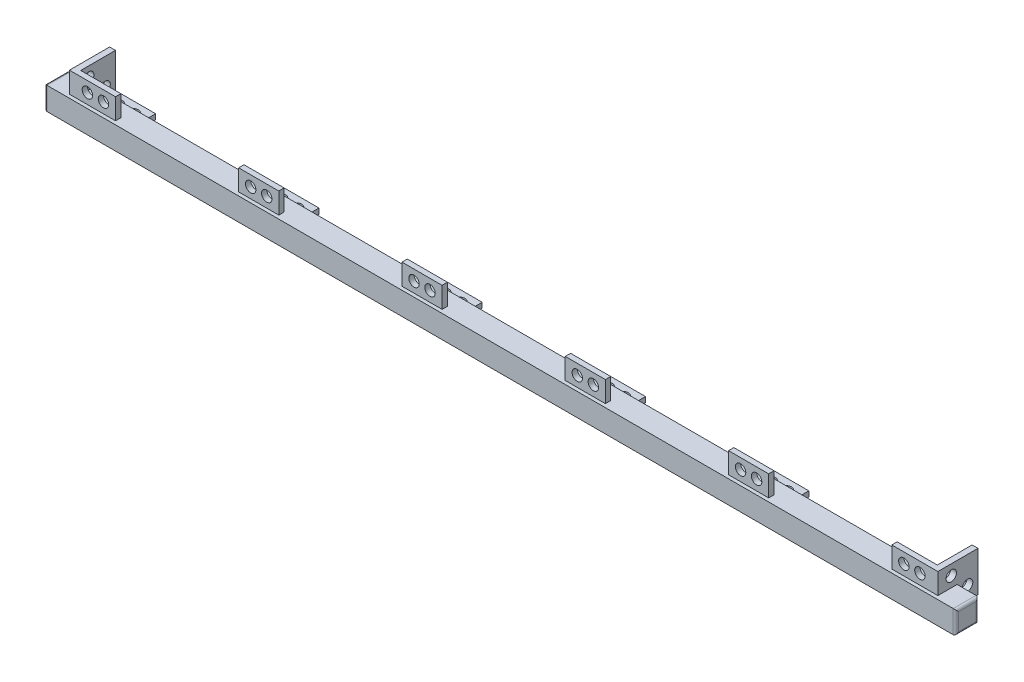
SolidWorks part; units mm, degrees
ref_plane "Front Plane" through (0, 0, 0) normal (0, 0, 1) x (1, 0, 0)
ref_plane "Top Plane" through (0, 0, 0) normal (0, 1, 0) x (1, 0, 0)
ref_plane "Right Plane" through (0, 0, 0) normal (1, 0, 0) x (0, 0, -1)
sketch "Sketch1" plane through (0, 0, 0) normal (1, 0, 0) x (0, 0, -1)
  line L1 (0, 0) -> (8.5, 0)
  line L2 (0, 0) -> (0, 8.5)
  line L3 (0, 8.5) -> (8.5, 8.5)
  line L4 (8.5, 0) -> (8.5, 8.5)
  dimension "D1" = 8.5
  dimension "D2" = 8.5
extrude "Boss-Extrude1" add sketch "Sketch1" along normal blind 340.5
sketch "Sketch2" plane through (0, 8.5, 0) normal (0, 1, 0) x (1, 0, 0)
  line L0 (340.5, 8.5) -> (0, 8.5) construction
  line L1 (6.75, 8.5) -> (333.75, 8.5) construction
  line L2 (6.75, 8.5) -> (6.75, 0) construction
  line L3 (6.75, 0) -> (333.75, 0) construction
  line L4 (333.75, 8.5) -> (333.75, 0) construction
  line L5 (340.5, 0) -> (0, 0) construction
  line L6 (340.5, 8.5) -> (340.5, 0) construction
  line L9 (0, 8.5) -> (0, 0) construction
  line L10 (17.75, 1.3) -> (17.75, 3.3) construction
  line L11 (10.25, 3.3) -> (25.25, 3.3)
  line L12 (10.25, 3.3) -> (10.25, 1.3)
  line L13 (10.25, 1.3) -> (25.25, 1.3)
  line L14 (25.25, 3.3) -> (25.25, 1.3)
  line L15 (71.25, 1.3) -> (86.25, 1.3)
  line L16 (71.25, 3.3) -> (71.25, 1.3)
  line L17 (71.25, 3.3) -> (86.25, 3.3)
  line L18 (86.25, 3.3) -> (86.25, 1.3)
  line L19 (132.25, 1.3) -> (147.25, 1.3)
  line L20 (132.25, 3.3) -> (132.25, 1.3)
  line L21 (132.25, 3.3) -> (147.25, 3.3)
  line L22 (147.25, 3.3) -> (147.25, 1.3)
  line L23 (193.25, 1.3) -> (208.25, 1.3)
  line L24 (193.25, 3.3) -> (193.25, 1.3)
  line L25 (193.25, 3.3) -> (208.25, 3.3)
  line L26 (208.25, 3.3) -> (208.25, 1.3)
  line L27 (254.25, 1.3) -> (269.25, 1.3)
  line L28 (254.25, 3.3) -> (254.25, 1.3)
  line L29 (254.25, 3.3) -> (269.25, 3.3)
  line L30 (269.25, 3.3) -> (269.25, 1.3)
  line L31 (315.25, 1.3) -> (330.25, 1.3)
  line L32 (315.25, 3.3) -> (315.25, 1.3)
  line L33 (315.25, 3.3) -> (330.25, 3.3)
  line L34 (330.25, 3.3) -> (330.25, 1.3)
  point P8 (340.5, 4.25)
  dimension "D1" = 327
  dimension "D2" = 6.75
  dimension "D3" = 6.75
  dimension "D4" = 2
  dimension "D5" = 15
  dimension "D6" = 11
  dimension "D8" = 1.3
  dimension "D7" = 6
extrude "Boss-Extrude2" add sketch "Sketch2" along normal blind 7.8
sketch "Sketch3" plane through (0, 0, -1.3) normal (0, 0, 1) x (1, 0, 0)
  line L0 (10.25, 8.5) -> (25.25, 8.5) construction
  line L3 (10.25, 16.3) -> (10.25, 8.5) construction
  circle A0 centre (14.75, 12.4) radius 1.95
  circle A1 centre (20.75, 12.4) radius 1.95
  circle A2 centre (75.75, 12.4) radius 1.95
  circle A3 centre (81.75, 12.4) radius 1.95
  circle A4 centre (136.75, 12.4) radius 1.95
  circle A5 centre (142.75, 12.4) radius 1.95
  circle A6 centre (197.75, 12.4) radius 1.95
  circle A7 centre (203.75, 12.4) radius 1.95
  circle A8 centre (258.75, 12.4) radius 1.95
  circle A9 centre (264.75, 12.4) radius 1.95
  circle A10 centre (319.75, 12.4) radius 1.95
  circle A11 centre (325.75, 12.4) radius 1.95
  dimension "D6" = 3.9
  dimension "D7" = 3.9
  dimension "D1" = 3.9
  dimension "D2" = 3.9
  dimension "D3" = 6
  dimension "D4" = 4.5
  dimension "D5" = 6
extrude "Cut-Extrude1" cut sketch "Sketch3" against normal blind 7.8
sketch "Sketch4" plane through (0, 0, -8.5) normal (0, 0, -1) x (-1, 0, 0)
  line L0 (-269.25, 1.3) -> (-254.25, 1.3)
  line L1 (-330.25, 3.3) -> (-315.25, 3.3)
  line L2 (-330.25, 3.3) -> (-330.25, 1.3)
  line L3 (-330.25, 1.3) -> (-315.25, 1.3)
  line L4 (-315.25, 3.3) -> (-315.25, 1.3)
  line L5 (-269.25, 3.3) -> (-269.25, 1.3)
  line L6 (-269.25, 3.3) -> (-254.25, 3.3)
  line L7 (-254.25, 3.3) -> (-254.25, 1.3)
  line L8 (-208.25, 1.3) -> (-193.25, 1.3)
  line L9 (-208.25, 3.3) -> (-208.25, 1.3)
  line L10 (-208.25, 3.3) -> (-193.25, 3.3)
  line L11 (-193.25, 3.3) -> (-193.25, 1.3)
  line L12 (-147.25, 1.3) -> (-132.25, 1.3)
  line L13 (-147.25, 3.3) -> (-147.25, 1.3)
  line L14 (-147.25, 3.3) -> (-132.25, 3.3)
  line L15 (-132.25, 3.3) -> (-132.25, 1.3)
  line L16 (-86.25, 1.3) -> (-71.25, 1.3)
  line L17 (-86.25, 3.3) -> (-86.25, 1.3)
  line L18 (-86.25, 3.3) -> (-71.25, 3.3)
  line L19 (-71.25, 3.3) -> (-71.25, 1.3)
  line L20 (-25.25, 1.3) -> (-10.25, 1.3)
  line L21 (-25.25, 3.3) -> (-25.25, 1.3)
  line L22 (-25.25, 3.3) -> (-10.25, 3.3)
  line L23 (-10.25, 3.3) -> (-10.25, 1.3)
  line L25 (-340.5, 0) -> (0, 0) construction
  dimension "D1" = 2
  dimension "D2" = 15
  dimension "D4" = 1.3
  dimension "D3" = 6
extrude "Boss-Extrude3" add sketch "Sketch4" along normal blind 7.8
sketch "Sketch5" plane through (0, 1.3, 0) normal (0, -1, 0) x (1, 0, 0)
  line L0 (330.25, -16.3) -> (330.25, -8.5) construction
  line L2 (330.25, -8.5) -> (315.25, -8.5) construction
  circle A0 centre (325.75, -12.4) radius 1.95
  circle A1 centre (319.75, -12.4) radius 1.95
  circle A2 centre (264.75, -12.4) radius 1.95
  circle A3 centre (258.75, -12.4) radius 1.95
  circle A4 centre (203.75, -12.4) radius 1.95
  circle A5 centre (197.75, -12.4) radius 1.95
  circle A6 centre (142.75, -12.4) radius 1.95
  circle A7 centre (136.75, -12.4) radius 1.95
  circle A8 centre (81.75, -12.4) radius 1.95
  circle A9 centre (75.75, -12.4) radius 1.95
  circle A10 centre (20.75, -12.4) radius 1.95
  circle A11 centre (14.75, -12.4) radius 1.95
  dimension "D1" = 3.9
  dimension "D2" = 3.9
  dimension "D3" = 6
  dimension "D4" = 4.5
  dimension "D6" = 3.9
  dimension "D5" = 6
extrude "Cut-Extrude2" cut sketch "Sketch5" against normal blind 7.8 contours A2 | A3 | A4 | A5 | A6 | A7 | A10 | A11 | A8 | A9 | A0 | A1 region at (264.75, 1.3, -12.4) region at (258.75, 1.3, -12.4) region at (203.75, 1.3, -12.4) region at (197.75, 1.3, -12.4) region at (142.75, 1.3, -12.4) region at (136.75, 1.3, -12.4) region at (81.75, 1.3, -12.4) region at (75.75, 1.3, -12.4) region at (20.75, 1.3, -12.4) region at (14.75, 1.3, -12.4)
fillet "Fillet1" radius 1 4 edges at (340.5, 0, -4.25) (340.5, 4.25, 0) (340.5, 8.5, -4.25) (340.5, 4.25, -8.5)
fillet "Fillet3" radius 1 4 edges at (0, 4.25, 0) (0, 0, -4.25) (0, 4.25, -8.5) (0, 8.5, -4.25)
sketch "Sketch6" plane through (10.25, 0, 0) normal (-1, 0, 0) x (0, 0, 1)
  line L0 (-16.3, 1.3) -> (-8.5, 1.3)
  line L1 (-8.5, 1.3) -> (-8.5, 3.3) construction
  line L2 (-16.3, 1.3) -> (-8.5, 1.3) construction
  line L3 (-8.5, 1.3) -> (-8.5, 8.5)
  line L4 (-8.5, 8.5) -> (-1.3, 8.5)
  line L5 (-1.3, 8.5) -> (-1.3, 16.3)
  line L6 (-1.3, 16.3) -> (-16.3, 16.3)
  line L7 (-16.3, 16.3) -> (-16.3, 1.3)
extrude "Boss-Extrude4" add sketch "Sketch6" along normal blind 2.2
sketch "Sketch7" plane through (330.25, 0, 0) normal (1, 0, 0) x (0, 0, -1)
  line L0 (8.5, 1.3) -> (16.3, 1.3)
  line L1 (16.3, 1.3) -> (16.3, 16.3)
  line L2 (16.3, 16.3) -> (1.3, 16.3)
  line L3 (1.3, 16.3) -> (1.3, 8.5)
  line L4 (1.3, 8.5) -> (8.5, 8.5)
  line L5 (8.5, 8.5) -> (8.5, 1.3)
extrude "Boss-Extrude5" add sketch "Sketch7" along normal blind 2.2
sketch "Sketch8" plane through (332.45, 0, 0) normal (1, 0, 0) x (0, 0, -1)
  line L0 (16.3, 16.3) -> (1.3, 16.3) construction
  line L1 (16.3, 1.3) -> (16.3, 16.3) construction
  circle A0 centre (6.3, 12.4) radius 1.95
  circle A1 centre (12.4, 6.3) radius 1.95
  dimension "D1" = 3.9
  dimension "D2" = 3.9
  dimension "D3" = 10
  dimension "D4" = 10
  dimension "D5" = 3.9
  dimension "D6" = 3.9
extrude "Cut-Extrude3" cut sketch "Sketch8" against normal blind 350
